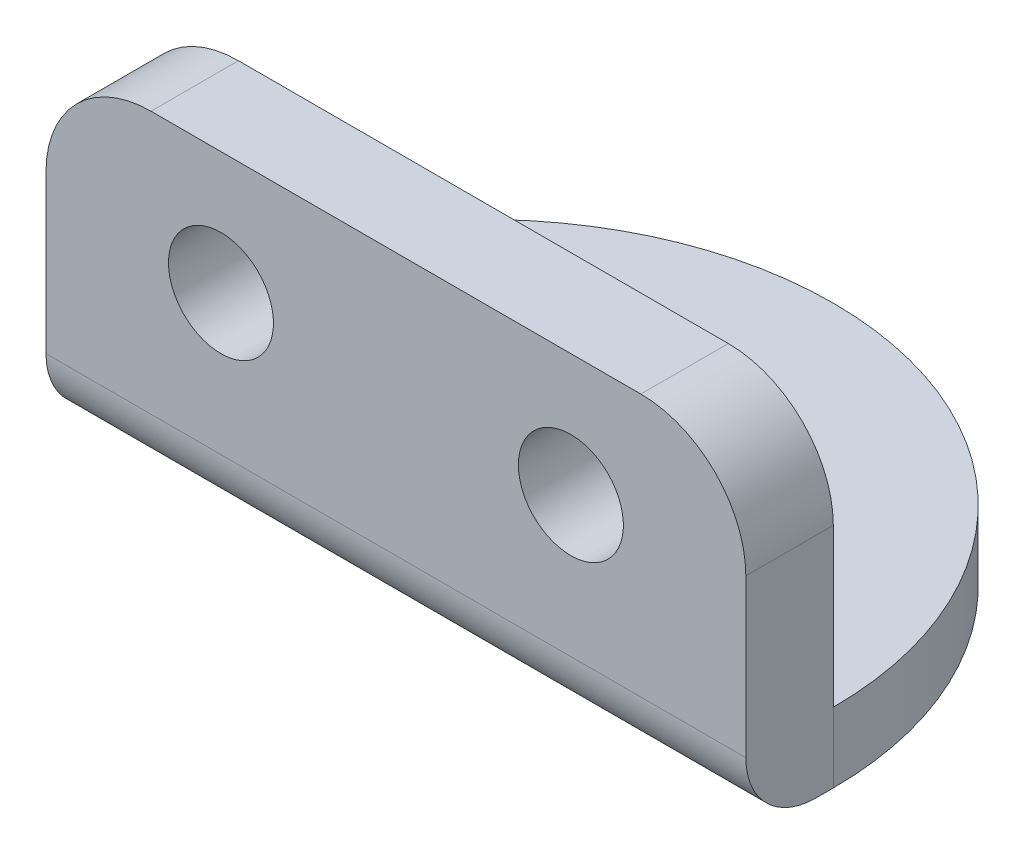
SolidWorks part; units mm, degrees
ref_plane "前视基准面" through (0, 0, 0) normal (0, 0, 1) x (1, 0, 0)
ref_plane "上视基准面" through (0, 0, 0) normal (0, 1, 0) x (1, 0, 0)
ref_plane "右视基准面" through (0, 0, 0) normal (1, 0, 0) x (0, 0, -1)
sketch "草图1" plane through (0, 0, 0) normal (0, 1, 0) x (1, 0, 0)
  line L0 (-36.8056, 0) -> (1803.476, 0) construction
  line L1 (0, -36.8056) -> (0, 1803.476) construction
  line L2 (-10, -3.23) -> (-10, -5.73)
  line L3 (-10, -5.73) -> (10, -5.73)
  line L4 (10, -5.73) -> (10, -3.23)
  line L5 (-10, -3.23) -> (10, -3.23)
  circle A0 centre (0, 0) radius 1.5
  arc A1 (10, -3.23) -> (-10, -3.23) centre (0, -3.23) ccw
  dimension "D1" = 3
  dimension "D2" = 10
  dimension "D3" = 2.5
  dimension "D4" = 5.73
extrude "凸台-拉伸2" add sketch "草图1" along normal blind 2 contours L5 A1 A0 region at (0, 0, -6.5464)
extrude "凸台-拉伸3" add sketch "草图1<5>" along normal blind 9.5 contours L5 L2 L3 L4 region at (0, 0, 4.48)
sketch "草图1<5>" plane through (0, 0, 0) normal (0, 1, 0) x (1, 0, 0) same geometry as "草图1"
sketch "草图2" plane through (0, 0, 3.23) normal (0, 0, -1) x (-1, 0, 0)
  line L0 (0, -1000) -> (0, 49000) construction
  line L1 (10, 9.5) -> (-10, 9.5) construction
  circle A0 centre (5, 6) radius 1.5
  circle A1 centre (-5, 6) radius 1.5
  point P11 (-1.0592, 7.3632)
  point P12 (-3.2752, 6.6106)
  dimension "D1" = 3
  dimension "D2" = 3.5
  dimension "D3" = 10
extrude "切除-拉伸1" cut sketch "草图2" against normal through all
fillet "圆角1" radius 3 2 edges at (10, 9.5, 4.48) (-10, 9.5, 4.48)
fillet "圆角2" radius 2 1 edges at (0, 0, 5.73)
